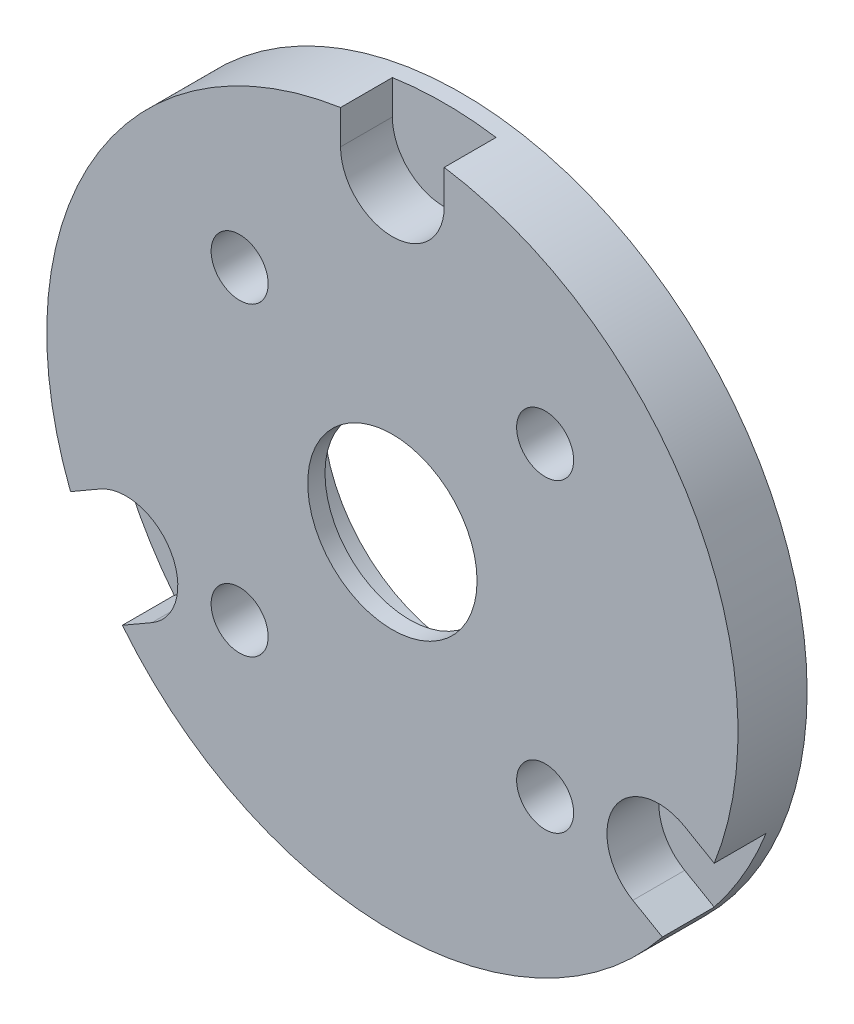
SolidWorks part; units mm, degrees
material "6061-T6 (SS)"
ref_plane "Front Plane" through (0, 0, 0) normal (0, 0, 1) x (1, 0, 0)
ref_plane "Top Plane" through (0, 0, 0) normal (0, 1, 0) x (1, 0, 0)
ref_plane "Right Plane" through (0, 0, 0) normal (1, 0, 0) x (0, 0, -1)
sketch "Sketch1" plane through (0, 0, 0) normal (0, 0, 1) x (1, 0, 0)
  circle A0 centre (0, 0) radius 20
  dimension "D1" = 40
extrude "Boss-Extrude1" add sketch "Sketch1" along normal blind 4
sketch "Sketch2" plane through (0, 0, 4) normal (0, 0, 1) x (1, 0, 0)
  line L0 (0, -2.2) -> (0, 2.2) construction
  line L1 (-3, 17.8) -> (-3, 25)
  line L2 (-3, 25) -> (3, 25)
  line L3 (3, 25) -> (3, 17.8)
  line L4 (2.2, 0) -> (-2.2, 0) construction
  line L5 (16.9153, -6.3019) -> (23.1506, -9.9019)
  line L6 (23.1506, -9.9019) -> (20.1506, -15.0981)
  line L7 (20.1506, -15.0981) -> (13.9153, -11.4981)
  line L8 (-13.9153, -11.4981) -> (-20.1506, -15.0981)
  line L9 (-20.1506, -15.0981) -> (-23.1506, -9.9019)
  line L10 (-23.1506, -9.9019) -> (-16.9153, -6.3019)
  arc A0 (-3, 17.8) -> (3, 17.8) centre (0, 17.8) ccw
  arc A1 (16.9153, -6.3019) -> (13.9153, -11.4981) centre (15.4153, -8.9) ccw
  arc A2 (-13.9153, -11.4981) -> (-16.9153, -6.3019) centre (-15.4153, -8.9) ccw
  dimension "D1" = 3
  dimension "D2" = 25
  dimension "D3" = 17.8
  dimension "D4" = 3
extrude "Cut-Extrude1" cut sketch "Sketch2" against normal blind 3
hole_wizard "M4x0.7 Tapped Hole1" positions "Sketch4" profile "Sketch3" tap size "M4x0.7" standard "Ansi Metric" end condition through all
sketch "Sketch4" plane through (0, 0, 4) normal (0, 0, 1) x (1, 0, 0)
  line L0 (0, 0) -> (-8.8388, 8.8388) construction
  line L3 (0, -2.2) -> (0, 2.2) construction
  point P0 (-8.8388, 8.8388)
  point P14 (8.8388, 8.8388)
  point P15 (8.8388, -8.8388)
  point P16 (-8.8388, -8.8388)
  dimension "D1" = 12.5
  dimension "D2" = 45
  dimension "D3" = 4
sketch "Sketch3" plane through (-8.8388, 8.8388, 4) normal (1, 0, 0) x (0, -1, 0)
  line L0 (0, 0) -> (0, 4)
  line L1 (0, 4) -> (1.65, 4)
  line L2 (1.65, 4) -> (1.65, 0)
  line L5 (1.65, 0) -> (0, 0)
  line L11 (0, -6.35) -> (0, 107.95) construction
  dimension "Thru Tap Drill Dia." = 3.3
  dimension "Thru Tap Drill Depth" = 4
cosmetic thread "Hole Thread1" parameters "D2"=4
cosmetic thread "Hole Thread2" parameters "D2"=4
cosmetic thread "Hole Thread3" parameters "D2"=4
cosmetic thread "Hole Thread4" parameters "D2"=4
sketch "Sketch5" plane through (0, 0, 4) normal (0, 0, 1) x (1, 0, 0)
  circle A0 centre (0, 0) radius 4.9
  dimension "D1" = 9.8
extrude "Cut-Extrude2" cut sketch "Sketch5" against normal through all
sketch "Sketch6" plane through (0, 0, 0) normal (0, 0, -1) x (-1, 0, 0)
  circle A0 centre (0, 0) radius 8
  dimension "D1" = 16
extrude "Cut-Extrude3" cut sketch "Sketch6" against normal blind 3
